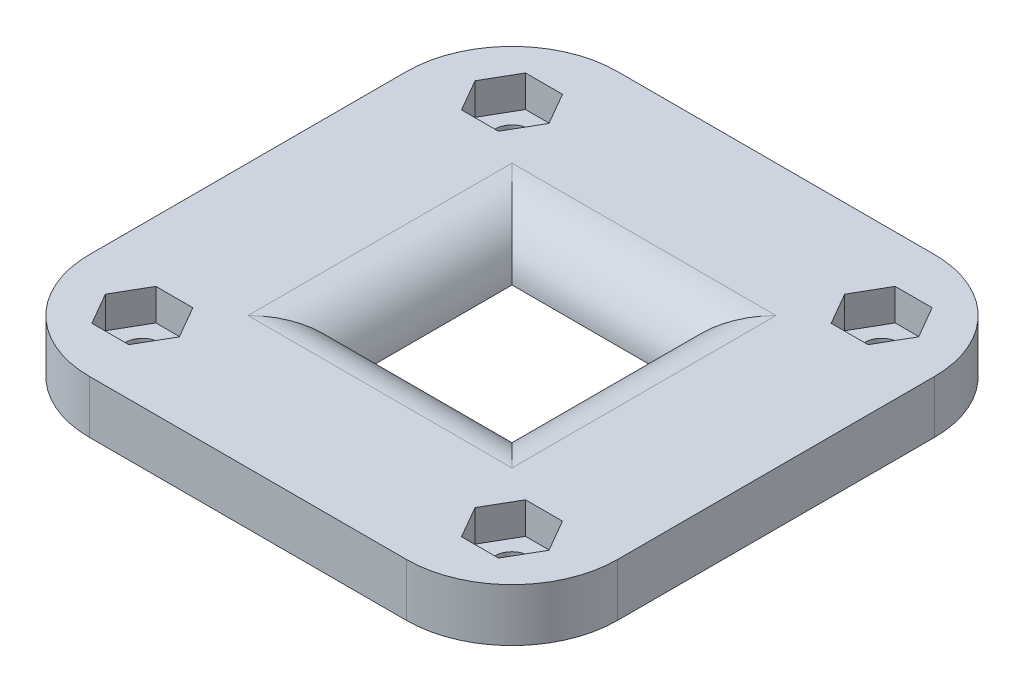
SolidWorks part; units mm, degrees
ref_plane "Front Plane" through (0, 0, 0) normal (0, 0, 1) x (1, 0, 0)
ref_plane "Top Plane" through (0, 0, 0) normal (0, 1, 0) x (1, 0, 0)
ref_plane "Right Plane" through (0, 0, 0) normal (1, 0, 0) x (0, 0, -1)
sketch "Sketch1" plane through (0, 0, 0) normal (0, 1, 0) x (1, 0, 0)
  line L1 (-64.5161, 31.9124) -> (-14.5161, 31.9124)
  line L2 (-64.5161, 31.9124) -> (-64.5161, -18.0876)
  line L3 (-64.5161, -18.0876) -> (-14.5161, -18.0876)
  line L4 (-14.5161, 31.9124) -> (-14.5161, -18.0876)
  dimension "D1" = 50
  dimension "D2" = 50
extrude "Boss-Extrude1" add sketch "Sketch1" along normal blind 5
sketch "Sketch2" plane through (0, 5, 0) normal (0, 1, 0) x (1, 0, 0)
  line L2 (-64.5161, -18.0876) -> (-14.5161, -18.0876) construction
  line L3 (-14.5161, -18.0876) -> (-14.5161, 31.9124) construction
  circle A0 centre (-57.0161, 24.4124) radius 1.6
  circle A1 centre (-22.0161, 24.4124) radius 1.6
  circle A2 centre (-57.0161, -10.5876) radius 1.6
  circle A3 centre (-22.0161, -10.5876) radius 1.6
  dimension "D1" = 35
  dimension "D3" = 3.2
  dimension "D2" = 35
  dimension "D4" = 7.5
  dimension "D5" = 7.5
extrude "Cut-Extrude1" cut sketch "Sketch2" against normal blind 5
sketch "Sketch4" plane through (0, 5, 0) normal (0, 1, 0) x (1, 0, 0)
  line L0 (-64.5161, 31.9124) -> (-14.5161, -18.0876) construction
  line L1 (-64.5161, -18.0876) -> (-14.5161, 31.9124) construction
  line L3 (-32.0161, -0.5876) -> (-47.0161, -0.5876)
  line L4 (-32.0161, -0.5876) -> (-32.0161, 14.4124)
  line L5 (-32.0161, 14.4124) -> (-47.0161, 14.4124)
  line L6 (-47.0161, -0.5876) -> (-47.0161, 14.4124)
  line L7 (-32.0161, -0.5876) -> (-47.0161, 14.4124) construction
  line L8 (-32.0161, 14.4124) -> (-47.0161, -0.5876) construction
  point P8 (-39.5161, 6.9124)
  dimension "D1" = 15
extrude "Cut-Extrude2" cut sketch "Sketch4" against normal blind 5 contours L3 L6 L5 L4
sketch "Sketch5" plane through (0, 5, 0) normal (0, 1, 0) x (1, 0, 0)
  line L0 (-14.5161, 31.9124) -> (-64.5161, 31.9124) construction
  line L1 (-58.7661, 27.4435) -> (-60.5161, 24.4124)
  line L2 (-60.5161, 24.4124) -> (-58.7661, 21.3814)
  line L3 (-58.7661, 21.3814) -> (-55.2661, 21.3814)
  line L4 (-55.2661, 21.3814) -> (-53.5161, 24.4124)
  line L5 (-53.5161, 24.4124) -> (-55.2661, 27.4435)
  line L6 (-55.2661, 27.4435) -> (-58.7661, 27.4435)
  line L7 (-23.7661, 27.4435) -> (-25.5161, 24.4124)
  line L8 (-25.5161, 24.4124) -> (-23.7661, 21.3814)
  line L9 (-23.7661, 21.3814) -> (-20.2661, 21.3814)
  line L10 (-20.2661, 21.3814) -> (-18.5161, 24.4124)
  line L11 (-18.5161, 24.4124) -> (-20.2661, 27.4435)
  line L12 (-20.2661, 27.4435) -> (-23.7661, 27.4435)
  line L13 (-58.7661, -7.5565) -> (-60.5161, -10.5876)
  line L14 (-60.5161, -10.5876) -> (-58.7661, -13.6186)
  line L15 (-58.7661, -13.6186) -> (-55.2661, -13.6186)
  line L16 (-55.2661, -13.6186) -> (-53.5161, -10.5876)
  line L17 (-53.5161, -10.5876) -> (-55.2661, -7.5565)
  line L18 (-55.2661, -7.5565) -> (-58.7661, -7.5565)
  line L19 (-23.7661, -7.5565) -> (-25.5161, -10.5876)
  line L20 (-25.5161, -10.5876) -> (-23.7661, -13.6186)
  line L21 (-23.7661, -13.6186) -> (-20.2661, -13.6186)
  line L22 (-20.2661, -13.6186) -> (-18.5161, -10.5876)
  line L23 (-18.5161, -10.5876) -> (-20.2661, -7.5565)
  line L24 (-20.2661, -7.5565) -> (-23.7661, -7.5565)
  circle A0 centre (-57.0161, 24.4124) radius 3.0311 construction
  circle A1 centre (-22.0161, 24.4124) radius 3.0311 construction
  circle A2 centre (-57.0161, -10.5876) radius 3.0311 construction
  circle A3 centre (-22.0161, -10.5876) radius 3.0311 construction
  dimension "D1" = 3.5
extrude "Cut-Extrude3" cut sketch "Sketch5" against normal blind 3
fillet "Fillet2" radius 10 4 edges at (-64.5161, 2.5, 18.0876) (-14.5161, 2.5, 18.0876) (-14.5161, 2.5, -31.9124) (-64.5161, 2.5, -31.9124)
fillet "Fillet3" radius 5 4 edges at (-39.5161, 5, -14.4124) (-32.0161, 5, -6.9124) (-39.5161, 5, 0.5876) (-47.0161, 5, -6.9124)
